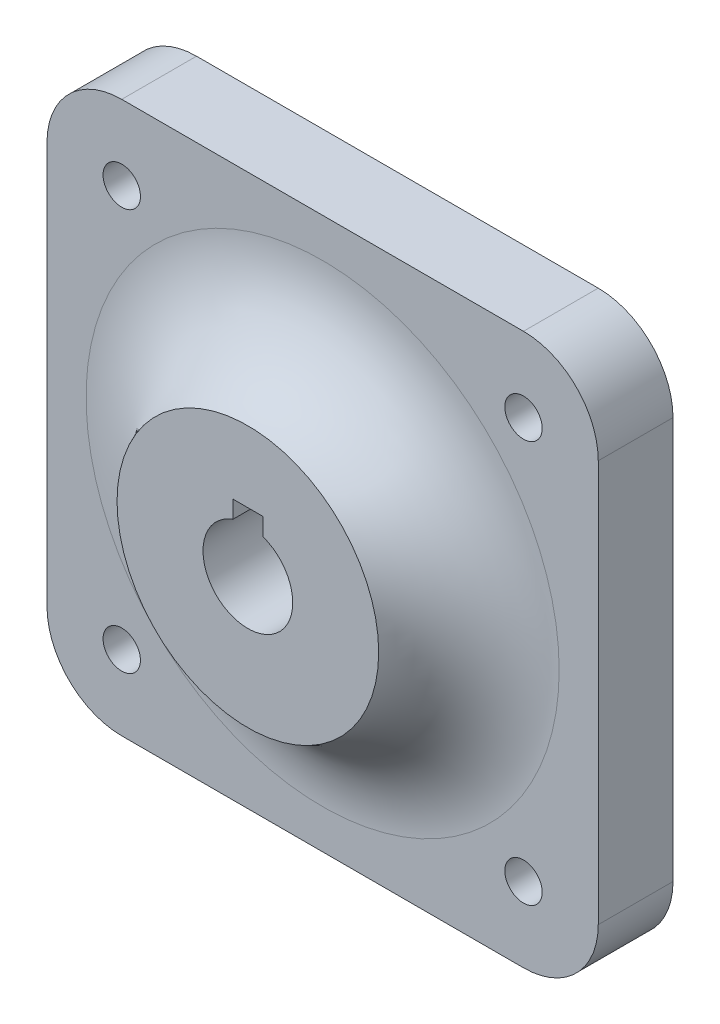
SolidWorks part; units mm, degrees
ref_plane "Front Plane" through (0, 0, 0) normal (0, 0, 1) x (1, 0, 0)
ref_plane "Top Plane" through (0, 0, 0) normal (0, 1, 0) x (1, 0, 0)
ref_plane "Right Plane" through (0, 0, 0) normal (1, 0, 0) x (0, 0, -1)
sketch "Spacing" plane through (0, 0, 0) normal (0, 0, 1) x (1, 0, 0)
  line L1 (-26.8701, -26.8701) -> (26.8701, -26.8701)
  line L2 (-26.8701, -26.8701) -> (-26.8701, 26.8701)
  line L3 (-26.8701, 26.8701) -> (26.8701, 26.8701)
  line L4 (26.8701, -26.8701) -> (26.8701, 26.8701)
  line L5 (-26.8701, -26.8701) -> (26.8701, 26.8701) construction
  line L6 (-26.8701, 26.8701) -> (26.8701, -26.8701) construction
  point P0 (0, 0)
  dimension "D1" = 76
sketch "Sketch1" plane through (0, 0, 7.9966) normal (0, 0, 1) x (1, 0, 0)
  line L0 (36.8701, -26.8701) -> (36.8701, 26.8701)
  line L1 (26.8701, 36.8701) -> (-26.8701, 36.8701)
  line L2 (-36.8701, 26.8701) -> (-36.8701, -26.8701)
  line L3 (26.8701, -36.8701) -> (-26.8701, -36.8701)
  arc A0 (26.8701, -36.8701) -> (36.8701, -26.8701) centre (26.8701, -26.8701) ccw
  arc A1 (-36.8701, -26.8701) -> (-26.8701, -36.8701) centre (-26.8701, -26.8701) ccw
  arc A2 (-26.8701, 36.8701) -> (-36.8701, 26.8701) centre (-26.8701, 26.8701) ccw
  arc A3 (36.8701, 26.8701) -> (26.8701, 36.8701) centre (26.8701, 26.8701) ccw
  circle A6 centre (26.8701, -26.8701) radius 2.5
  circle A7 centre (-26.8701, -26.8701) radius 2.5
  circle A8 centre (-26.8701, 26.8701) radius 2.5
  circle A9 centre (26.8701, 26.8701) radius 2.5
  dimension "D1" = 20
  dimension "D2" = 5
extrude "Boss-Extrude1" add sketch "Sketch1" along normal blind 10
sketch "Sketch2" plane through (0, 0, 7.9966) normal (0, 0, -1) x (-1, 0, 0)
  circle A0 centre (0, 0) radius 15
  dimension "D1" = 30
extrude "Cut-Extrude1" cut sketch "Sketch2" against normal blind 12.5
sketch "Sketch3" plane through (0, 0, 17.9966) normal (0, 0, 1) x (1, 0, 0)
  circle A0 centre (0, 0) radius 17.5
  dimension "D1" = 35
extrude "Boss-Extrude2" add sketch "Sketch3" along normal blind 10
fillet "Fillet1" radius 15 1 edges at (17.5, 0, 17.9966)
sketch "Sketch4" plane through (0, 0, 27.9966) normal (0, 0, 1) x (1, 0, 0)
  circle A0 centre (0, 0) radius 6
  dimension "D1" = 12
extrude "Cut-Extrude2" cut sketch "Sketch4" against normal through all
sketch "Sketch5" plane through (0, 0, 27.9966) normal (0, 0, 1) x (1, 0, 0)
  line L1 (2, 8) -> (-2, 8)
  line L2 (2, 8) -> (2, 5.6569)
  line L3 (2, 5.6569) -> (-2, 5.6569)
  line L4 (-2, 8) -> (-2, 5.6569)
  line L5 (2, 8) -> (-2, 5.6569) construction
  line L6 (2, 5.6569) -> (-2, 8) construction
  circle A0 centre (0, 0) radius 6 construction
  point P0 (0, 6.8284)
  point P7 (0, 0)
  dimension "D1" = 4
  dimension "D2" = 2
extrude "Cut-Extrude3" cut sketch "Sketch5" against normal through all
